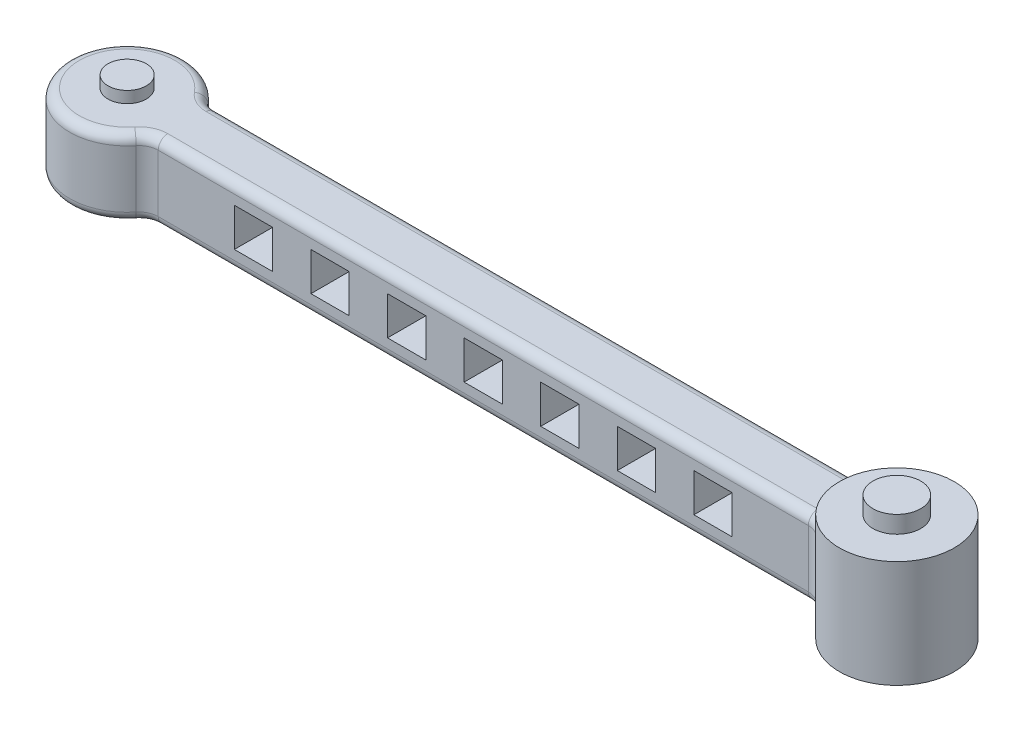
SolidWorks part; units mm, degrees
ref_plane "前视基准面" through (0, 0, 0) normal (0, 0, 1) x (1, 0, 0)
ref_plane "上视基准面" through (0, 0, 0) normal (0, 1, 0) x (1, 0, 0)
ref_plane "右视基准面" through (0, 0, 0) normal (1, 0, 0) x (0, 0, -1)
other "Configuration Table"
sketch "草图1" plane through (0, 0, 0) normal (0, 0, 1) x (1, 0, 0)
  line L1 (-175, 10) -> (175, 10)
  line L2 (-175, 10) -> (-175, -10)
  line L3 (-175, -10) -> (175, -10)
  line L4 (175, 10) -> (175, -10)
  line L5 (-175, 10) -> (175, -10) construction
  line L6 (-175, -10) -> (175, 10) construction
  point P0 (0, 0)
  dimension "D1" = 350
  dimension "D2" = 20
extrude "凸台-拉伸1" add sketch "草图1" along normal blind 30
sketch "草图3" plane through (0, 0, 30) normal (0, 0, 1) x (1, 0, 0)
sketch "草图7" plane through (0, -10, 0) normal (0, -1, 0) x (-1, 0, 0)
  line L0 (-55, 0) -> (55, 0) construction
  line L1 (-175, -30) -> (-175, 0) construction
  line L2 (-175, 0) -> (-175, -30)
  arc A0 (-175, -30) -> (-175, 0) centre (-200.9808, -15) cw
extrude "凸台-拉伸3" add sketch "草图7" against normal blind 20
fillet "圆角2" radius 10 1 edges at (175, 0, 0)
fillet "圆角3" radius 10 1 edges at (175, 0, 30)
mirror "镜向2" about plane through (0, 0, 0) normal (1, 0, 0) of "凸台-拉伸3", "圆角3", "圆角2"
sketch "草图9" plane through (0, 10, 0) normal (0, 1, 0) x (1, 0, 0)
  circle A0 centre (-200.9808, -15) radius 10
sketch "草图10" plane through (0, -10, 0) normal (0, -1, 0) x (-1, 0, 0)
  circle A0 centre (-200.9808, -15) radius 30
extrude "凸台-拉伸4" add sketch "草图10" along normal blind 18
sketch "草图11" plane through (0, -28, 0) normal (0, -1, 0) x (-1, 0, 0)
  circle A0 centre (-200.9808, -15) radius 12.5
extrude "凸台-拉伸5" add sketch "草图11" along normal blind 9
mirror "镜向4" about plane through (0, 0, 0) normal (0, 1, 0) of "凸台-拉伸4"
mirror "镜向5" about plane through (0, 0, 0) normal (0, 1, 0) of "凸台-拉伸5"
sketch "草图12" plane through (0, 10, 0) normal (0, 1, 0) x (1, 0, 0)
  line L1 (-40.7, 0) -> (40.7, 0) construction
  line L3 (-169.7558, 0) -> (169.7558, 0)
  line L4 (169.7558, -30) -> (-169.7558, -30)
  arc A0 (-177.562, 3.75) -> (-169.7558, 0) centre (-169.7558, 10) ccw construction
  arc A1 (-169.7558, 0) -> (-177.562, 3.75) centre (-169.7558, 10) cw
  arc A2 (-169.7558, -30) -> (-177.562, -33.75) centre (-169.7558, -40) ccw
  arc A3 (-177.562, 3.75) -> (-177.562, -33.75) centre (-200.9808, -15) cw
  arc A4 (169.7558, 0) -> (177.562, 3.75) centre (169.7558, 10) ccw
  arc A5 (169.7558, -30) -> (177.562, -33.75) centre (169.7558, -40) cw
  arc A6 (177.562, 3.75) -> (177.562, -33.75) centre (200.9808, -15) ccw
extrude "凸台-拉伸6" add sketch "草图12" along normal blind 10
mirror "镜向6" about plane through (0, 0, 0) normal (0, 1, 0) of "凸台-拉伸6"
sketch "草图14" plane through (0, -10, 0) normal (0, -1, 0) x (-1, 0, 0)
  circle A0 centre (200.9808, -15) radius 30
extrude "凸台-拉伸7" add sketch "草图14" along normal blind 10 and the other way up to surface
sketch "草图15" plane through (0, 20, 0) normal (0, 1, 0) x (1, 0, 0)
  circle A0 centre (-200.9808, -15) radius 10
extrude "凸台-拉伸8" add sketch "草图15" along normal blind 6
sketch "草图17" plane through (0, 0, 0) normal (0, 0, -1) x (-1, 0, 0)
  line L1 (-10, 10) -> (10, 10)
  line L2 (-10, 10) -> (-10, -10)
  line L3 (-10, -10) -> (10, -10)
  line L4 (10, 10) -> (10, -10)
  line L5 (-10, 10) -> (10, -10) construction
  line L6 (-10, -10) -> (10, 10) construction
  point P0 (0, 0)
  dimension "D1" = 20
  dimension "D2" = 20
extrude "切除-拉伸1" cut sketch "草图17" against normal through all
pattern_linear "阵列(线性)2" count 4 spacing 40 along (-1, 0, 0) count 4 spacing 40 along (1, 0, 0) of "切除-拉伸1"
fillet "圆角7" radius 5 14 edges at (-174.0859, 20, -0.9861) (-174.0859, 20, 30.9861) (0, 20, 30) (174.0859, 20, 30.9861) (174.0859, 20, -0.9861) (0, 20, 0) (-174.0859, -20, -0.9861) (0, -20, 0) (174.0859, -20, -0.9861) (174.0859, -20, 30.9861) (0, -20, 30) (-174.0859, -20, 30.9861) (-230.9808, 20, 15) (-230.9808, -20, 15)
